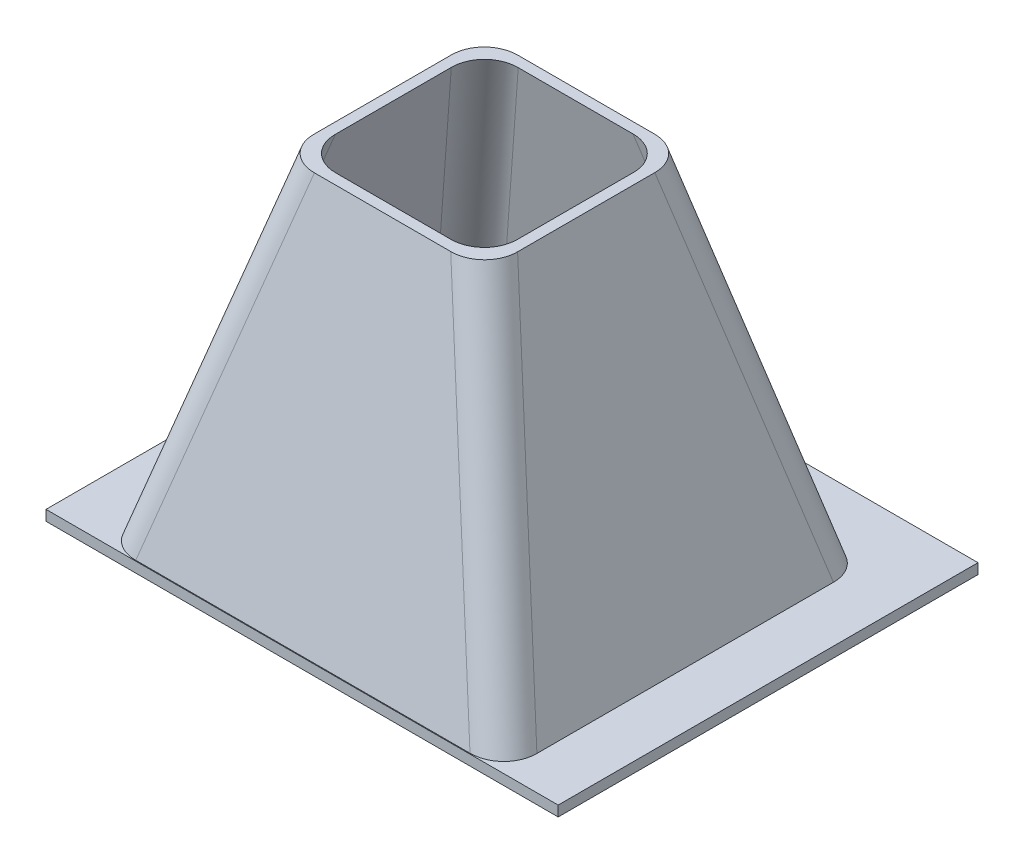
SolidWorks part; units mm, degrees
ref_plane "Front Plane" through (0, 0, 0) normal (0, 0, 1) x (1, 0, 0)
ref_plane "Top Plane" through (0, 0, 0) normal (0, 1, 0) x (1, 0, 0)
ref_plane "Right Plane" through (0, 0, 0) normal (1, 0, 0) x (0, 0, -1)
sketch "Sketch1" plane through (0, 0, 0) normal (0, 1, 0) x (1, 0, 0)
  line L1 (-29.5, -29.5) -> (29.5, -29.5)
  line L2 (-29.5, -29.5) -> (-29.5, 29.5)
  line L3 (-29.5, 29.5) -> (29.5, 29.5)
  line L4 (29.5, -29.5) -> (29.5, 29.5)
  line L5 (-29.5, -29.5) -> (29.5, 29.5) construction
  line L6 (-29.5, 29.5) -> (29.5, -29.5) construction
  point P0 (0, 0)
  dimension "D1" = 59
  dimension "D2" = 59
extrude "Boss-Extrude1" add sketch "Sketch1" against normal blind 100
ref_plane "Plane1" through (0, -100, 0) normal (0, 1, 0) x (1, 0, 0)
draft "Draft1" type of draft neutral plane draft angle 13 faces to draft 2 face at (0, -50, 29.5) face at (0, -50, -29.5) neutral plane through (0, 0, 0) neutral plane normal (0, 1, 0) parameters "D1"=13
draft "Draft2" type of draft neutral plane draft angle 16 faces to draft 2 face at (-29.5, -50, 0) face at (29.5, -50, 0) neutral plane through (0, 0, 0) neutral plane normal (0, 1, 0) parameters "D1"=16
shell "Shell1" thickness 3
sketch "Sketch7" plane through (0, -97, 0) normal (0, 1, 0) x (1, 0, 0)
  line L1 (54.1934, -48.8153) -> (-54.1934, -48.8153)
  line L2 (54.1934, -48.8153) -> (54.1934, 48.8153)
  line L3 (54.1934, 48.8153) -> (-54.1934, 48.8153)
  line L4 (-54.1934, -48.8153) -> (-54.1934, 48.8153)
  line L5 (54.1934, -48.8153) -> (-54.1934, 48.8153) construction
  line L6 (54.1934, 48.8153) -> (-54.1934, -48.8153) construction
  point P0 (0, 0)
extrude "Cut-Extrude3" cut sketch "Sketch7" against normal up to next
sketch "Sketch8" plane through (0, -100, 0) normal (0, -1, 0) x (1, 0, 0)
  line L0 (-54.1934, 48.8153) -> (54.1934, 48.8153) construction
  line L1 (-74.1934, -68.8153) -> (74.1934, -68.8153)
  line L2 (-74.1934, -68.8153) -> (-74.1934, 68.8153)
  line L3 (-74.1934, 68.8153) -> (74.1934, 68.8153)
  line L4 (74.1934, -68.8153) -> (74.1934, 68.8153)
  line L5 (-74.1934, -68.8153) -> (74.1934, 68.8153) construction
  line L6 (-74.1934, 68.8153) -> (74.1934, -68.8153) construction
  line L7 (54.1934, -48.8153) -> (-54.1934, -48.8153)
  line L8 (54.1934, -48.8153) -> (54.1934, 48.8153)
  line L9 (54.1934, 48.8153) -> (-54.1934, 48.8153)
  line L10 (-54.1934, -48.8153) -> (-54.1934, 48.8153)
  line L11 (54.1934, -48.8153) -> (-54.1934, 48.8153) construction
  line L12 (54.1934, 48.8153) -> (-54.1934, -48.8153) construction
  line L13 (-54.1934, -48.8153) -> (-54.1934, 48.8153) construction
  point P0 (0, 0)
  point P6 (0, 0)
  dimension "D1" = 0
  dimension "D2" = 20
  dimension "D3" = 20
extrude "Boss-Extrude7" add sketch "Sketch8" along normal blind 3
fillet "Fillet5" radius 10 8 edges at (-43.8373, -50, -41.0434) (43.8373, -50, -41.0434) (40.2863, -48.5, 37.6182) (43.8373, -50, 41.0434) (-43.8373, -50, 41.0434) (40.2863, -48.5, -37.6182) (-40.2863, -48.5, -37.6182) (-40.2863, -48.5, 37.6182)
sketch "Sketch9" plane through (0, -100, 0) normal (0, 1, 0) x (1, 0, 0)
  line L0 (0, -56.65) -> (0, 56.65) construction
  line L1 (-51.2782, 48.8153) -> (51.2782, 48.8153) construction
  circle A0 centre (0, 57.8153) radius 3.5
  dimension "D2" = 7
  dimension "D1" = 9
extrude "Cut-Extrude4" cut sketch "Sketch9" against normal blind 3
sketch "Sketch10" plane through (0, -103, 0) normal (0, -1, 0) x (1, 0, 0)
  line L0 (74.1934, -68.8153) -> (74.1934, 68.8153) construction
  line L1 (-74.1934, 68.8153) -> (74.1934, 68.8153)
  line L2 (-74.1934, 68.8153) -> (-74.1934, 52.8153)
  line L3 (-74.1934, 52.8153) -> (74.1934, 52.8153)
  line L4 (74.1934, 68.8153) -> (74.1934, 52.8153)
  dimension "D1" = 16
extrude "Cut-Extrude5" cut sketch "Sketch10" against normal up to next
